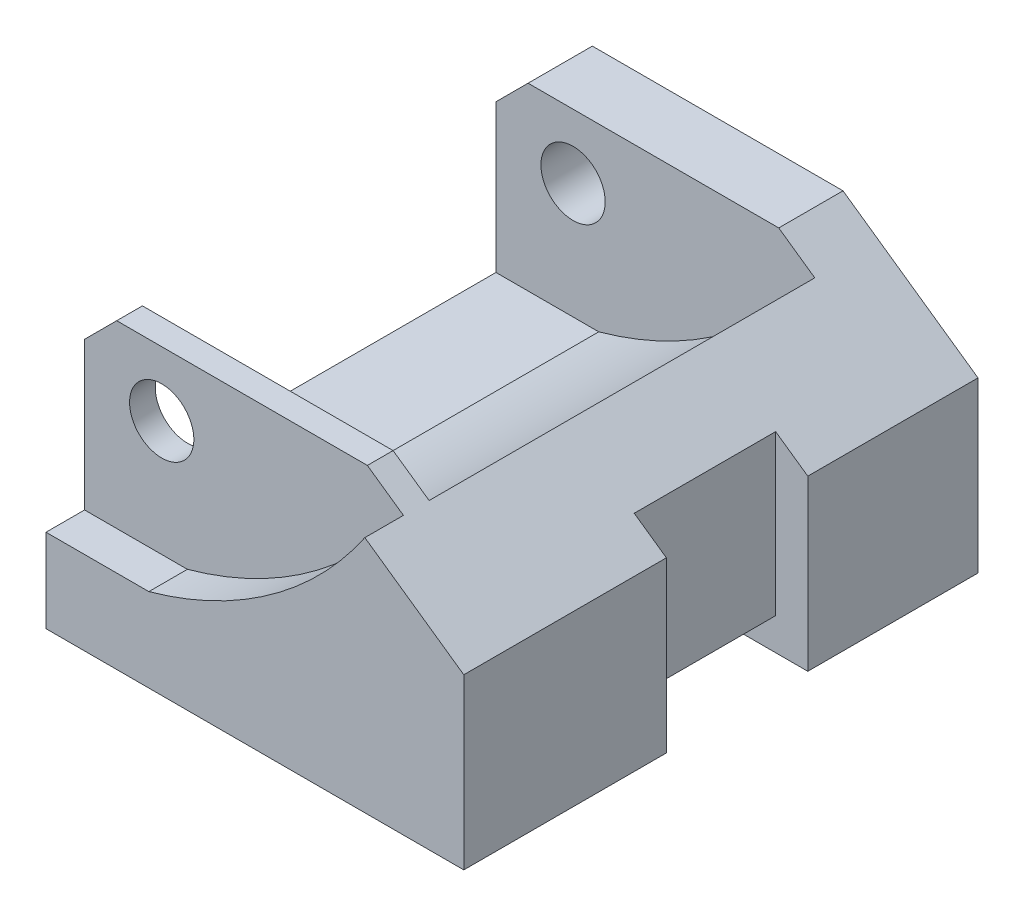
SolidWorks part; units mm, degrees
ref_plane "Front Plane" through (0, 0, 0) normal (0, 0, 1) x (1, 0, 0)
ref_plane "Top Plane" through (0, 0, 0) normal (0, 1, 0) x (1, 0, 0)
ref_plane "Right Plane" through (0, 0, 0) normal (1, 0, 0) x (0, 0, -1)
sketch "Sketch1" plane through (0, 0, 0) normal (0, 0, 1) x (1, 0, 0)
  line L0 (60, 29.7967) -> (60, 5)
  line L1 (0, 0) -> (65, 0)
  line L2 (0, 0) -> (0, 36)
  line L3 (5, 41) -> (44, 41)
  line L4 (65, 0) -> (65, 26.2956)
  line L5 (60, 5) -> (0, 5)
  line L6 (0, 13) -> (16, 13)
  line L7 (44, 41) -> (65, 26.2956)
  line L8 (0, 36) -> (5, 41)
  arc A0 (16, 13) -> (49.606, 37.0746) centre (0, 70.8273) ccw
  circle A1 centre (12, 31) radius 5
  point P1 (65, 41)
  point P2 (0, 41)
  point P11 (0, 0)
  dimension "D5" = 120
  dimension "D10" = 10
  dimension "D1" = 65
  dimension "D2" = 41
  dimension "D3" = 16
  dimension "D4" = 28
  dimension "D6" = 21
  dimension "D7" = 35
  dimension "D8" = 5
  dimension "D9" = 5
  dimension "D11" = 12
  dimension "D12" = 10
  dimension "D13" = 5
  dimension "D14" = 45
extrude "Boss-Extrude9" add sketch "Sketch1" along normal mid plane 80 contours L6 A0 L7 L3 L8 L2 A1 region at (21.1888, 28.511, 0)
sketch "Sketch6" plane through (0, 41, 0) normal (0, 1, 0) x (1, 0, 0)
  line L0 (0, -40) -> (0, 40) construction
  line L1 (0, 30) -> (49.606, 30)
  line L2 (0, 30) -> (0, -30)
  line L3 (0, -30) -> (49.606, -30)
  line L4 (49.606, 30) -> (49.606, -30)
  line L5 (5, -40) -> (44, -40) construction
  line L6 (0, -34) -> (49.606, -34)
  line L7 (0, -34) -> (0, -40)
  line L8 (0, -40) -> (49.606, -40)
  line L9 (49.606, -34) -> (49.606, -40)
  line L10 (60, 0) -> (0, 0) construction
  line L11 (-2.8216, 0) -> (8.7527, 0) construction
  dimension "D1" = 60
  dimension "D2" = 6
extrude "Cut-Extrude5" cut sketch "Sketch6" against normal blind 40
extrude "Boss-Extrude11" add sketch "Sketch1<13>" along normal mid plane 80 separate body contours L7 L0 L5 L2 L1 L4 region at (62.0899, 27.4604, 0)
sketch "Sketch1<13>" plane through (0, 0, 0) normal (0, 0, 1) x (1, 0, 0) same geometry as "Sketch1"
sketch "Sketch7" plane through (65, 0, 0) normal (1, 0, 0) x (0, 0, -1)
  line L0 (-40, 0) -> (40, 0) construction
  line L1 (13.5188, 0) -> (-8.4812, 0)
  line L2 (13.5188, 0) -> (13.5188, 29.7967)
  line L3 (13.5188, 29.7967) -> (-8.4812, 29.7967)
  line L4 (-8.4812, 0) -> (-8.4812, 29.7967)
  dimension "D1" = 22
extrude "Cut-Extrude6" cut sketch "Sketch7" against normal blind 80
extrude "Boss-Extrude12" add sketch "Sketch1<14>" along normal mid plane 80 contours A0 L6 L2 L5 L0 L7 region at (38.2703, 15.4274, 0)
sketch "Sketch1<14>" plane through (0, 0, 0) normal (0, 0, 1) x (1, 0, 0) same geometry as "Sketch1"
